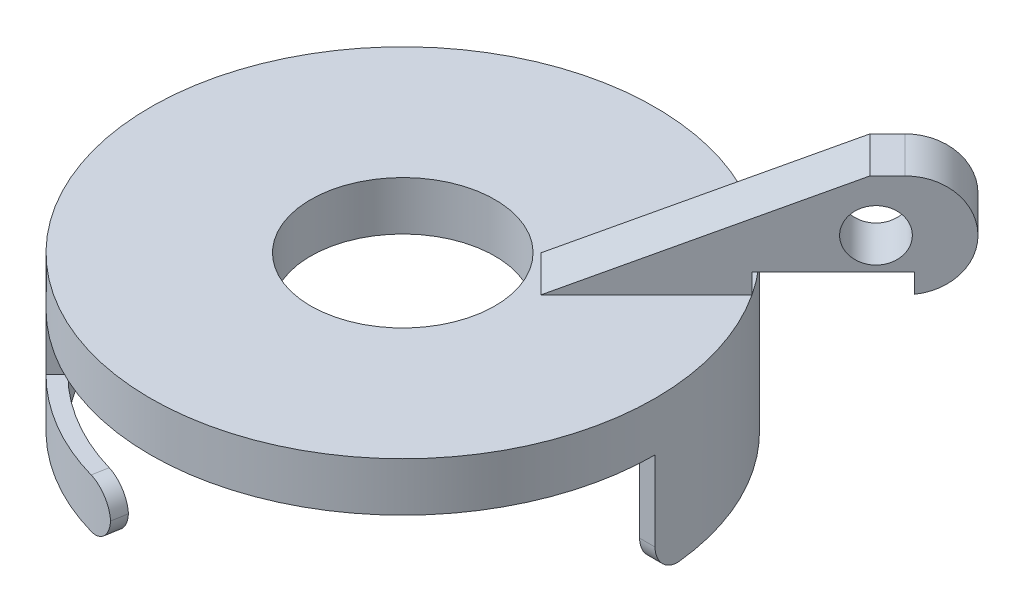
SolidWorks part; units mm, degrees
material "ABS"
ref_plane "前视" through (0, 0, 0) normal (0, 0, 1) x (1, 0, 0)
ref_plane "上视" through (0, 0, 0) normal (0, 1, 0) x (1, 0, 0)
ref_plane "右视" through (0, 0, 0) normal (1, 0, 0) x (0, 0, -1)
sketch "草图1" plane through (0, 0, 0) normal (0, 1, 0) x (1, 0, 0)
  circle A0 centre (0, 0) radius 22.25
  circle A1 centre (0, 0) radius 24.5
  dimension "D1" = 44.5
  dimension "D2" = 49
extrude "凸台-拉伸1" add sketch "草图1" along normal blind 4.75 contours A1
sketch "草图4" plane through (0, 0, 0) normal (0, -1, 0) x (1, 0, 0)
  line L1 (-23, 0) -> (-24.5, 0)
  line L2 (23, 0) -> (24.5, 0)
  line L4 (-16.2635, 16.2635) -> (-17.3241, 17.3241)
  line L5 (17.3241, -17.3241) -> (16.2635, -16.2635)
  arc A0 (-16.2635, 16.2635) -> (-23, 0) centre (0, 0) ccw
  arc A1 (-17.3241, 17.3241) -> (-24.5, 0) centre (0, 0) ccw
  arc A2 (16.2635, -16.2635) -> (23, 0) centre (0, 0) ccw
  circle A3 centre (0, 0) radius 23 construction
  circle A4 centre (0, 0) radius 24.5 construction
  arc A5 (17.3241, -17.3241) -> (24.5, 0) centre (0, 0) ccw
  point P1 (23.6446, 7.2289)
  point P14 (21.2778, 6.5053)
  dimension "D1" = 46
  dimension "D2" = 49
  dimension "D3" = 1.5
extrude "凸台-拉伸2" add sketch "草图4" along normal blind 5.5
sketch "草图5" plane through (0, -5.5, 0) normal (0, -1, 0) x (1, 0, 0)
  line L1 (-23, 0) -> (-24.5, 0)
  line L2 (3.9939, -22.6506) -> (4.2544, -24.1278)
  line L3 (23, 0) -> (24.5, 0)
  line L4 (-4.2544, 24.1278) -> (-3.9939, 22.6506)
  arc A0 (-3.9939, 22.6506) -> (-23, 0) centre (0, 0) ccw
  arc A1 (-4.2544, 24.1278) -> (-24.5, 0) centre (0, 0) ccw
  arc A2 (3.9939, -22.6506) -> (23, 0) centre (0, 0) ccw
  arc A3 (4.2544, -24.1278) -> (24.5, 0) centre (0, 0) ccw
  arc A7 (24.5, 0) -> (-17.3241, 17.3241) centre (0, 0) ccw construction
  dimension "D1" = 23
  dimension "D2" = 80
  dimension "D3" = 80
  dimension "D4" = 80
  dimension "D5" = 80
extrude "凸台-拉伸3" add sketch "草图5" along normal blind 4.75
sketch "草图6" plane through (0, 4.75, 0) normal (0, 1, 0) x (1, 0, 0)
  circle A0 centre (0, 0) radius 8.95
  dimension "D1" = 17.9
extrude "切除-拉伸1" cut sketch "草图6" against normal through all
sketch "草图7" plane through (0, 4.75, 0) normal (0, 1, 0) x (1, 0, 0)
  line L0 (0, 0) -> (0, 50000) construction
  line L1 (0, 0) -> (17.4832, 17.4832) construction
  dimension "D1" = 45
ref_plane "基准面1" through (0, 0, 0) normal (0.7071, 0, 0.7071) x (0.7071, 0, -0.7071)
sketch "草图8" plane through (0, 0, 0) normal (0.7071, 0, 0.7071) x (0.7071, 0, -0.7071)
  line L0 (-141421.3562, 4.75) -> (176776.6953, 4.75) construction
  line L1 (9.5, 4.75) -> (39.5, 4.75)
  line L2 (9.5, 4.75) -> (9.5, 14.75)
  line L3 (9.5, 14.75) -> (39.5, 14.75)
  line L4 (39.5, 4.75) -> (39.5, 14.75)
  line L5 (24.5, 0) -> (24.5, 4.75) construction
  point P6 (24.5, 4.75)
  dimension "D1" = 30
  dimension "D2" = 10
extrude "凸台-拉伸4" add sketch "草图8" along normal blind 5
fillet "圆角1" radius 10 1 edges at (8.4853, 14.75, -4.9497)
fillet "圆角2" radius 5 2 edges at (29.6985, 14.75, -26.163) (29.6985, 4.75, -26.163)
hole_wizard "大小mm 暗销孔1" positions "草图9" profile "草图10" hole size "Ø5.0" standard "ISO" end condition through all
sketch "草图9" plane through (3.5355, 0, 3.5355) normal (0.7071, 0, 0.7071) x (0.7071, 0, -0.7071)
  point P0 (32.4944, 9.75)
  dimension "D1" = 8.51
  dimension "D2" = 5
sketch "草图10" plane through (26.5125, 9.75, -19.4415) normal (0, 1, 0) x (0.7071, 0, -0.7071)
  line L0 (0, 0) -> (0, 42.0741)
  line L1 (0, 42.0741) -> (2.5, 42.0741)
  line L2 (2.5, 42.0741) -> (2.5, 0)
  line L5 (2.5, 0) -> (0, 0)
  line L11 (0, -6.35) -> (0, 107.95) construction
  dimension "通孔孔直径" = 5
  dimension "通孔孔深度" = 42.0741
sketch "草图11" plane through (3.5355, 0, 3.5355) normal (0.7071, 0, 0.7071) x (0.7071, 0, -0.7071)
  line L1 (23.9844, 4.75) -> (35.1529, 4.75)
  line L2 (23.9844, 4.75) -> (23.9844, 6.6765)
  line L3 (23.9844, 6.6765) -> (35.1529, 6.6765)
  line L4 (35.1529, 4.75) -> (35.1529, 6.6765)
extrude "切除-拉伸2" cut sketch "草图11" against normal through all
sketch "草图12" plane through (0, 0, 0) normal (-0.7071, 0, -0.7071) x (-0.7071, 0, 0.7071)
  line L0 (-32.0815, 14.75) -> (-9.5, 4.75)
  line L1 (-34.5, 14.75) -> (-19.5, 14.75) construction
  line L2 (-19.5, 14.75) -> (-32.0815, 14.75)
  arc A0 (-9.5, 4.75) -> (-19.5, 14.75) centre (-19.5, 4.75) ccw
  arc A1 (-9.5, 4.75) -> (-19.5, 14.75) centre (-19.5, 4.75) ccw construction
extrude "切除-拉伸3" cut sketch "草图12" against normal through all
fillet "圆角3" radius 2.5 6 edges at (-23.75, -10.25, 0) (4.1241, -10.25, -23.3892) (4.1241, -5.5, -23.3892) (23.75, -10.25, 0) (-4.1241, -5.5, 23.3892) (-4.1241, -10.25, 23.3892)
